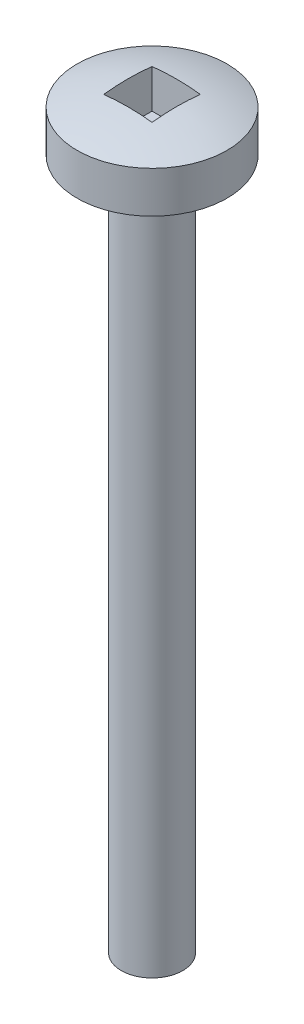
SolidWorks part; units mm, degrees
ref_plane "Front Plane" through (0, 0, 0) normal (0, 0, 1) x (1, 0, 0)
ref_plane "Top Plane" through (0, 0, 0) normal (0, 1, 0) x (1, 0, 0)
ref_plane "Right Plane" through (0, 0, 0) normal (1, 0, 0) x (0, 0, -1)
sketch "Sketch1" plane through (0, 0, 0) normal (0, 1, 0) x (1, 0, 0)
  circle A0 centre (0, 0) radius 1.1303
  dimension "D1" = 2.2606
extrude "threads" add sketch "Sketch1" against normal blind 25.4
sketch "Sketch2" plane through (0, 0, 0) normal (0, 1, 0) x (1, 0, 0)
  circle A0 centre (0, 0) radius 2.7559
  dimension "D1" = 5.5118
extrude "Head" add sketch "Sketch2" along normal blind 1.524
dome "HeadDome" faces to dome 1 distance 0.508 reverse direction no elliptical dome no face at (0, 1.524, 2.7559) parameters "D1"=0.508
ref_plane "DriverPlane" through (0, 2.032, 0) normal (0, 1, 0) x (1, 0, 0)
sketch "Sketch3" plane through (0, 2.032, 0) normal (0, 1, 0) x (1, 0, 0)
  line L1 (-0.889, -0.889) -> (0.889, -0.889)
  line L2 (-0.889, -0.889) -> (-0.889, 0.889)
  line L3 (-0.889, 0.889) -> (0.889, 0.889)
  line L4 (0.889, -0.889) -> (0.889, 0.889)
  line L5 (-0.889, -0.889) -> (0.889, 0.889) construction
  line L6 (-0.889, 0.889) -> (0.889, -0.889) construction
  point P0 (0, 0)
  dimension "D1" = 1.778
extrude "Driver" cut sketch "Sketch3" against normal blind 1.524
